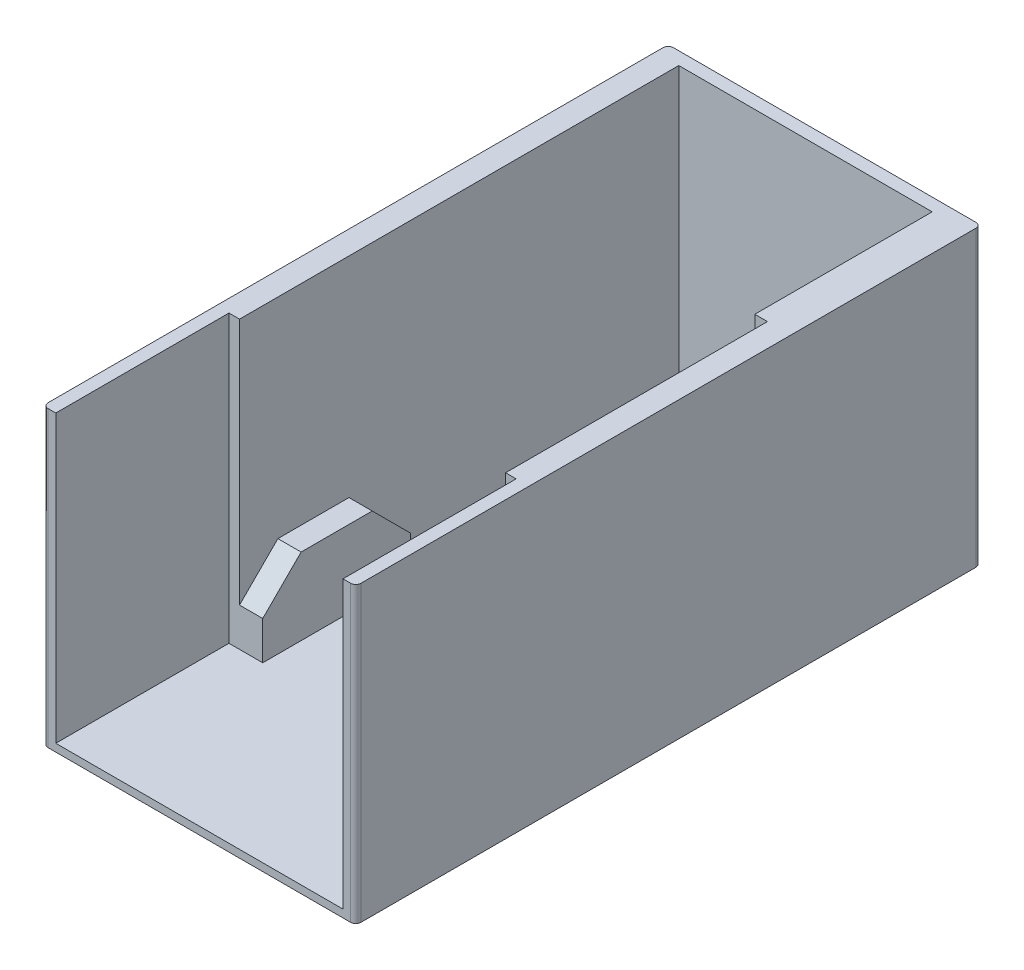
SolidWorks part; units mm, degrees
ref_plane "Front Plane" through (0, 0, 0) normal (0, 0, 1) x (1, 0, 0)
ref_plane "Top Plane" through (0, 0, 0) normal (0, 1, 0) x (1, 0, 0)
ref_plane "Right Plane" through (0, 0, 0) normal (1, 0, 0) x (0, 0, -1)
sketch "Sketch1" plane through (0, 0, 0) normal (0, 1, 0) x (1, 0, 0)
  line L0 (0, 0) -> (0, 2095.5) construction
  line L1 (-863.6, -520.7) -> (863.6, -520.7)
  line L2 (-863.6, -520.7) -> (-863.6, 520.7)
  line L3 (-863.6, 520.7) -> (863.6, 520.7)
  line L4 (863.6, -520.7) -> (863.6, 520.7)
  line L5 (-863.6, -520.7) -> (863.6, 520.7) construction
  line L6 (-863.6, 520.7) -> (863.6, -520.7) construction
  line L7 (-660.4, 520.7) -> (660.4, 520.7)
  line L8 (-660.4, 520.7) -> (-660.4, 1409.7)
  line L9 (-660.4, 1409.7) -> (660.4, 1409.7)
  line L10 (660.4, 520.7) -> (660.4, 1409.7)
  line L12 (-800.1, 1409.7) -> (800.1, 1409.7)
  line L13 (-800.1, 1409.7) -> (-800.1, 2095.5)
  line L14 (-800.1, 2095.5) -> (800.1, 2095.5)
  line L15 (800.1, 1409.7) -> (800.1, 2095.5)
  line L16 (-800.1, 2095.5) -> (723.9, 2095.5)
  line L17 (-800.1, 2095.5) -> (-800.1, 3162.3)
  line L18 (-800.1, 3162.3) -> (723.9, 3162.3)
  line L19 (723.9, 2095.5) -> (723.9, 3162.3)
  point P0 (0, 0)
  point P10 (0, 1409.7)
  point P13 (0, 2095.5)
  dimension "D1" = 1727.2
  dimension "D2" = 1041.4
  dimension "D3" = 1320.8
  dimension "D4" = 889
  dimension "D5" = 1600.2
  dimension "D6" = 685.8
  dimension "D7" = 1524
  dimension "D8" = 1066.8
sketch "Sketch2" plane through (0, 0, 0) normal (0, 1, 0) x (1, 0, 0)
  line L0 (-275, 3062.3) -> (-275, 3012.3) construction
  line L1 (-450, 3012.3) -> (-100, 3012.3)
  line L2 (-450, 3012.3) -> (-450, 2512.3)
  line L3 (-450, 2512.3) -> (-100, 2512.3)
  line L4 (-100, 3012.3) -> (-100, 2512.3)
  line L5 (-500, 3062.3) -> (-50, 3062.3)
  line L6 (-500, 3062.3) -> (-500, 2462.3)
  line L7 (-500, 2462.3) -> (-50, 2462.3)
  line L8 (-50, 3062.3) -> (-50, 2462.3)
  line L9 (-450, 2762.3) -> (-500, 2762.3) construction
  line L10 (100, 3012.3) -> (100, 2512.3)
  line L11 (100, 3012.3) -> (450, 3012.3)
  line L12 (450, 3012.3) -> (450, 2512.3)
  line L13 (100, 2512.3) -> (450, 2512.3)
  line L14 (50, 3062.3) -> (50, 2462.3)
  line L15 (50, 3062.3) -> (500, 3062.3)
  line L16 (500, 3062.3) -> (500, 2462.3)
  line L17 (50, 2462.3) -> (500, 2462.3)
  line L18 (100, 2312.3) -> (100, 1812.3)
  line L19 (100, 2312.3) -> (450, 2312.3)
  line L20 (450, 2312.3) -> (450, 1812.3)
  line L21 (100, 1812.3) -> (450, 1812.3)
  line L22 (50, 2362.3) -> (50, 1762.3)
  line L23 (50, 2362.3) -> (500, 2362.3)
  line L24 (500, 2362.3) -> (500, 1762.3)
  line L25 (50, 1762.3) -> (500, 1762.3)
  line L26 (100, 1612.3) -> (100, 1112.3)
  line L27 (100, 1612.3) -> (450, 1612.3)
  line L28 (450, 1612.3) -> (450, 1112.3)
  line L29 (100, 1112.3) -> (450, 1112.3)
  line L30 (50, 1662.3) -> (50, 1062.3)
  line L31 (50, 1662.3) -> (500, 1662.3)
  line L32 (500, 1662.3) -> (500, 1062.3)
  line L33 (50, 1062.3) -> (500, 1062.3)
  line L34 (100, 912.3) -> (100, 412.3)
  line L35 (100, 912.3) -> (450, 912.3)
  line L36 (450, 912.3) -> (450, 412.3)
  line L37 (100, 412.3) -> (450, 412.3)
  line L38 (50, 962.3) -> (50, 362.3)
  line L39 (50, 962.3) -> (500, 962.3)
  line L40 (500, 962.3) -> (500, 362.3)
  line L41 (50, 362.3) -> (500, 362.3)
  line L42 (-450, 2312.3) -> (-450, 1812.3)
  line L43 (-450, 2312.3) -> (-100, 2312.3)
  line L44 (-100, 2312.3) -> (-100, 1812.3)
  line L45 (-450, 1812.3) -> (-100, 1812.3)
  line L46 (-500, 2362.3) -> (-500, 1762.3)
  line L47 (-500, 2362.3) -> (-50, 2362.3)
  line L48 (-50, 2362.3) -> (-50, 1762.3)
  line L49 (-500, 1762.3) -> (-50, 1762.3)
  line L50 (-450, 1612.3) -> (-450, 1112.3)
  line L51 (-450, 1612.3) -> (-100, 1612.3)
  line L52 (-100, 1612.3) -> (-100, 1112.3)
  line L53 (-450, 1112.3) -> (-100, 1112.3)
  line L54 (-500, 1662.3) -> (-500, 1062.3)
  line L55 (-500, 1662.3) -> (-50, 1662.3)
  line L56 (-50, 1662.3) -> (-50, 1062.3)
  line L57 (-500, 1062.3) -> (-50, 1062.3)
  line L58 (-450, 912.3) -> (-450, 412.3)
  line L59 (-450, 912.3) -> (-100, 912.3)
  line L60 (-100, 912.3) -> (-100, 412.3)
  line L61 (-450, 412.3) -> (-100, 412.3)
  line L62 (-500, 962.3) -> (-500, 362.3)
  line L63 (-500, 962.3) -> (-50, 962.3)
  line L64 (-50, 962.3) -> (-50, 362.3)
  line L65 (-500, 362.3) -> (-50, 362.3)
  line L66 (-450, 3012.3) -> (100, 3012.3) construction
  line L67 (-450, 3012.3) -> (-450, 2312.3) construction
  line L68 (-50, 3062.3) -> (50, 3062.3) construction
  line L69 (0, 3062.3) -> (0, 2095.5) construction
  line L70 (-500, 2462.3) -> (-500, 2362.3)
  line L71 (-550, 3112.3) -> (550, 3112.3)
  line L72 (-550, 3112.3) -> (-550, 312.3)
  line L73 (-550, 312.3) -> (550, 312.3)
  line L74 (550, 3112.3) -> (550, 312.3)
  line L75 (-800.1, 3162.3) -> (723.9, 3162.3) construction
  dimension "D1" = 350
  dimension "D2" = 500
  dimension "D3" = 450
  dimension "D4" = 600
  dimension "D5" = 2
  dimension "D7" = 90
  dimension "D8" = 550
  dimension "D9" = 50
  dimension "D10" = 50
  dimension "D11" = 50
  dimension "D12" = 50
  dimension "D13" = 100
  dimension "D14" = 50
  dimension "D6" = 4
sketch "Resized Everything" plane through (0, 0, 0) normal (0, 1, 0) x (1, 0, 0)
  line L85 (-790.321, 2977.388) -> (-697.865, 2977.388)
  line L86 (-697.865, 2977.388) -> (-697.865, 3039.618)
  line L87 (-790.321, 3039.618) -> (-697.865, 3039.618)
  line L88 (-790.321, 2977.388) -> (-790.321, 3039.618)
  line L89 (-804.545, 2904.49) -> (-683.641, 2904.49)
  line L90 (-683.641, 2904.49) -> (-683.641, 2977.388)
  line L91 (-804.545, 2977.388) -> (-683.641, 2977.388)
  line L92 (-804.545, 2904.49) -> (-804.545, 2977.388)
  line L93 (-800.1, 3039.618) -> (-800.1, 3087.624)
  line L94 (-800.1, 3039.618) -> (-688.086, 3039.618)
  line L95 (-688.086, 3039.618) -> (-688.086, 3087.624)
  line L96 (-800.1, 3087.624) -> (-688.086, 3087.624)
  line L97 (-800.1, 3087.624) -> (-693.42, 3087.624)
  line L98 (-693.42, 3087.624) -> (-693.42, 3162.3)
  line L99 (-800.1, 3162.3) -> (-693.42, 3162.3)
  line L100 (-800.1, 3087.624) -> (-800.1, 3162.3)
  line L101 (-779.093, 3113.3) -> (-779.093, 3106.3)
  line L102 (-779.093, 3113.3) -> (-747.593, 3113.3)
  line L103 (-747.593, 3155.3) -> (-747.593, 3113.3)
  line L104 (-779.093, 3155.3) -> (-747.593, 3155.3)
  line L105 (-779.093, 3155.3) -> (-779.093, 3113.3)
  line L106 (-775.593, 3151.8) -> (-751.093, 3151.8)
  line L107 (-751.093, 3151.8) -> (-751.093, 3116.8)
  line L108 (-775.593, 3116.8) -> (-751.093, 3116.8)
  line L109 (-775.593, 3151.8) -> (-775.593, 3116.8)
  line L110 (-740.593, 3106.3) -> (-740.593, 3064.3)
  line L111 (-740.593, 3064.3) -> (-709.093, 3064.3)
  line L112 (-709.093, 3106.3) -> (-709.093, 3064.3)
  line L113 (-740.593, 3106.3) -> (-709.093, 3106.3)
  line L114 (-737.093, 3102.8) -> (-737.093, 3067.8)
  line L115 (-737.093, 3067.8) -> (-712.593, 3067.8)
  line L116 (-712.593, 3102.8) -> (-712.593, 3067.8)
  line L117 (-737.093, 3102.8) -> (-712.593, 3102.8)
  line L118 (-740.593, 3155.3) -> (-740.593, 3113.3)
  line L119 (-740.593, 3113.3) -> (-709.093, 3113.3)
  line L120 (-709.093, 3155.3) -> (-709.093, 3113.3)
  line L121 (-740.593, 3155.3) -> (-709.093, 3155.3)
  line L122 (-737.093, 3151.8) -> (-737.093, 3116.8)
  line L123 (-737.093, 3151.8) -> (-712.593, 3151.8)
  line L124 (-712.593, 3151.8) -> (-712.593, 3116.8)
  line L125 (-737.093, 3116.8) -> (-712.593, 3116.8)
  line L126 (-740.593, 3008.3) -> (-740.593, 2966.3)
  line L127 (-740.593, 2966.3) -> (-709.093, 2966.3)
  line L128 (-709.093, 3008.3) -> (-709.093, 2966.3)
  line L129 (-740.593, 3008.3) -> (-709.093, 3008.3)
  line L130 (-737.093, 3004.8) -> (-737.093, 2969.8)
  line L131 (-737.093, 2969.8) -> (-712.593, 2969.8)
  line L132 (-712.593, 3004.8) -> (-712.593, 2969.8)
  line L133 (-737.093, 3004.8) -> (-712.593, 3004.8)
  line L134 (-740.593, 3057.3) -> (-740.593, 3015.3)
  line L135 (-740.593, 3015.3) -> (-709.093, 3015.3)
  line L136 (-709.093, 3057.3) -> (-709.093, 3015.3)
  line L137 (-740.593, 3057.3) -> (-709.093, 3057.3)
  line L138 (-737.093, 3053.8) -> (-737.093, 3018.8)
  line L139 (-737.093, 3053.8) -> (-712.593, 3053.8)
  line L140 (-712.593, 3053.8) -> (-712.593, 3018.8)
  line L141 (-737.093, 3018.8) -> (-712.593, 3018.8)
  line L142 (-779.093, 3057.3) -> (-779.093, 3015.3)
  line L143 (-779.093, 3015.3) -> (-747.593, 3015.3)
  line L144 (-747.593, 3057.3) -> (-747.593, 3015.3)
  line L145 (-779.093, 3057.3) -> (-747.593, 3057.3)
  line L146 (-775.593, 3053.8) -> (-775.593, 3018.8)
  line L147 (-775.593, 3018.8) -> (-751.093, 3018.8)
  line L148 (-751.093, 3053.8) -> (-751.093, 3018.8)
  line L149 (-775.593, 3053.8) -> (-751.093, 3053.8)
  line L150 (-779.093, 3106.3) -> (-779.093, 3064.3)
  line L151 (-779.093, 3064.3) -> (-747.593, 3064.3)
  line L152 (-747.593, 3106.3) -> (-747.593, 3064.3)
  line L153 (-779.093, 3106.3) -> (-747.593, 3106.3)
  line L154 (-775.593, 3102.8) -> (-775.593, 3067.8)
  line L155 (-775.593, 3102.8) -> (-751.093, 3102.8)
  line L156 (-751.093, 3102.8) -> (-751.093, 3067.8)
  line L157 (-775.593, 3067.8) -> (-751.093, 3067.8)
  line L158 (-782.593, 3158.8) -> (-705.593, 3158.8)
  line L159 (-705.593, 3158.8) -> (-705.593, 2962.8)
  line L160 (-782.593, 2962.8) -> (-705.593, 2962.8)
  line L161 (-782.593, 3158.8) -> (-782.593, 2962.8)
  line L162 (-779.093, 3008.3) -> (-779.093, 2966.3)
  line L163 (-779.093, 2966.3) -> (-747.593, 2966.3)
  line L164 (-747.593, 3008.3) -> (-747.593, 2966.3)
  line L165 (-779.093, 3008.3) -> (-747.593, 3008.3)
  line L166 (-775.593, 3004.8) -> (-775.593, 2969.8)
  line L167 (-775.593, 3004.8) -> (-751.093, 3004.8)
  line L168 (-751.093, 3004.8) -> (-751.093, 2969.8)
  line L169 (-775.593, 2969.8) -> (-751.093, 2969.8)
sketch "Sketch6" plane through (0, 0, 0) normal (0, 1, 0) x (1, 0, 0)
  line L0 (-800.1, 3162.3) -> (723.9, 3162.3) construction
  line L1 (-748.0935, 2917.905) -> (-748.0935, 3167.3) construction
  line L2 (-809.2275, 2917.905) -> (-686.9595, 2917.905)
  line L3 (-686.9595, 2917.905) -> (-686.9595, 3167.3)
  line L4 (-686.9595, 3167.3) -> (-809.2275, 3167.3)
  line L5 (-696.087, 3048.381) -> (-696.087, 2990.596)
  line L6 (-800.1, 3048.381) -> (-800.1, 2990.596)
  line L7 (-809.2275, 2917.905) -> (-809.2275, 3167.3)
  line L8 (-701.04, 3162.3) -> (-696.087, 3162.3)
  line L9 (-696.087, 3162.3) -> (-696.087, 3092.958)
  line L10 (-804.2275, 2922.905) -> (-809.2275, 2922.905)
  line L11 (-691.9595, 2922.905) -> (-686.9595, 2922.905)
  line L16 (-791.0195, 2990.596) -> (-705.1675, 2990.596)
  line L17 (-705.1675, 2990.596) -> (-705.1675, 3048.381)
  line L18 (-791.0195, 3048.381) -> (-705.1675, 3048.381)
  line L19 (-791.0195, 2990.596) -> (-791.0195, 3048.381)
  line L20 (-804.2275, 2922.905) -> (-691.9595, 2922.905)
  line L21 (-691.9595, 2922.905) -> (-691.9595, 2990.596)
  line L22 (-804.2275, 2990.596) -> (-691.9595, 2990.596)
  line L23 (-804.2275, 2922.905) -> (-804.2275, 2990.596)
  line L24 (-800.1, 3048.381) -> (-800.1, 3092.958)
  line L25 (-800.1, 3048.381) -> (-696.087, 3048.381)
  line L26 (-696.087, 3048.381) -> (-696.087, 3092.958)
  line L27 (-800.1, 3092.958) -> (-696.087, 3092.958)
  line L28 (-800.1, 3092.958) -> (-701.04, 3092.958)
  line L29 (-701.04, 3092.958) -> (-701.04, 3162.3)
  line L30 (-800.1, 3162.3) -> (-701.04, 3162.3)
  line L31 (-800.1, 3092.958) -> (-800.1, 3162.3)
  point P3 (-748.0935, 2922.905)
  dimension "D1" = 239.395
  dimension "D2" = 5
  dimension "D3" = 5
  dimension "D4" = 5
extrude "Boss-Extrude1" add sketch "Sketch6" along normal blind 111.8 contours L2 L1 L20 L23 L22 L6 L24 L31 L30 L4 L7 | L1 L2 L3 L4 L30 L29 L27 L26 L5 L22 L21 L20 | L29 L27 L9 L8 region at (-801.3852, 0, -3070.3406) region at (-694.8018, 0, -3070.3406) region at (-698.5635, 0, -3127.629)
sketch "Sketch7" plane through (0, 0, 0) normal (0, -1, 0) x (1, 0, 0)
  line L0 (-800.1, -3048.381) -> (-800.1, -2990.596) construction
  line L1 (-696.087, -3048.381) -> (-696.087, -2990.596) construction
  line L2 (-800.1, -3048.381) -> (-800.1, -3092.958) construction
  line L3 (-800.1, -3092.958) -> (-696.087, -3092.958) construction
  line L4 (-800.1, -3092.958) -> (-701.04, -3092.958) construction
  line L5 (-701.04, -3092.958) -> (-701.04, -3162.3) construction
  line L6 (-800.1, -3162.3) -> (-701.04, -3162.3) construction
  line L7 (-800.1, -3092.958) -> (-800.1, -3162.3) construction
  line L8 (-701.04, -3162.3) -> (-696.087, -3162.3) construction
  line L9 (-696.087, -3162.3) -> (-696.087, -3092.958) construction
  line L10 (-696.087, -3048.381) -> (-696.087, -3092.958) construction
  line L11 (-800.1, -3048.381) -> (-696.087, -3048.381) construction
  line L12 (-809.2275, -2917.905) -> (-686.9595, -2917.905) construction
  line L13 (-686.9595, -2917.905) -> (-686.9595, -3167.3) construction
  line L14 (-686.9595, -3167.3) -> (-809.2275, -3167.3) construction
  line L15 (-809.2275, -2917.905) -> (-809.2275, -3167.3) construction
  line L16 (-804.2275, -2922.905) -> (-691.9595, -2922.905) construction
  line L17 (-691.9595, -2922.905) -> (-691.9595, -2990.596) construction
  line L18 (-804.2275, -2990.596) -> (-691.9595, -2990.596) construction
  line L19 (-804.2275, -2922.905) -> (-804.2275, -2990.596) construction
  line L20 (-705.1675, -2990.596) -> (-705.1675, -3048.381) construction
  line L21 (-791.0195, -3048.381) -> (-705.1675, -3048.381) construction
  line L22 (-791.0195, -2990.596) -> (-791.0195, -3048.381) construction
  line L23 (-791.0195, -2990.596) -> (-705.1675, -2990.596) construction
  line L24 (-800.1, -3048.381) -> (-800.1, -2990.596)
  line L25 (-696.087, -3048.381) -> (-696.087, -2990.596)
  line L26 (-800.1, -3048.381) -> (-800.1, -3092.958)
  line L27 (-800.1, -3092.958) -> (-696.087, -3092.958)
  line L28 (-800.1, -3092.958) -> (-701.04, -3092.958)
  line L29 (-701.04, -3092.958) -> (-701.04, -3162.3)
  line L30 (-800.1, -3162.3) -> (-701.04, -3162.3)
  line L31 (-800.1, -3092.958) -> (-800.1, -3162.3)
  line L32 (-701.04, -3162.3) -> (-696.087, -3162.3)
  line L33 (-696.087, -3162.3) -> (-696.087, -3092.958)
  line L34 (-696.087, -3048.381) -> (-696.087, -3092.958)
  line L35 (-800.1, -3048.381) -> (-696.087, -3048.381)
  line L36 (-809.2275, -2917.905) -> (-686.9595, -2917.905)
  line L37 (-686.9595, -2917.905) -> (-686.9595, -3167.3)
  line L38 (-686.9595, -3167.3) -> (-809.2275, -3167.3)
  line L39 (-809.2275, -2917.905) -> (-809.2275, -3167.3)
  line L40 (-804.2275, -2922.905) -> (-691.9595, -2922.905)
  line L41 (-691.9595, -2922.905) -> (-691.9595, -2990.596)
  line L42 (-804.2275, -2990.596) -> (-691.9595, -2990.596)
  line L43 (-804.2275, -2922.905) -> (-804.2275, -2990.596)
  line L44 (-705.1675, -2990.596) -> (-705.1675, -3048.381)
  line L45 (-791.0195, -3048.381) -> (-705.1675, -3048.381)
  line L46 (-791.0195, -2990.596) -> (-791.0195, -3048.381)
  line L47 (-791.0195, -2990.596) -> (-705.1675, -2990.596)
extrude "Boss-Extrude2" add sketch "Sketch7" along normal blind 3 contours L39 L38 L37 L36
sketch "Sketch8" plane through (0, 0, 0) normal (0, 1, 0) x (1, 0, 0)
  line L0 (-691.9595, 2922.905) -> (-686.9595, 2922.905) construction
  line L1 (-804.2275, 2922.905) -> (-809.2275, 2922.905) construction
  line L2 (-800.1, 3048.381) -> (-800.1, 2990.596) construction
  line L3 (-696.087, 3048.381) -> (-696.087, 2990.596) construction
  line L4 (-800.1, 3048.381) -> (-800.1, 3092.958) construction
  line L5 (-800.1, 3092.958) -> (-696.087, 3092.958) construction
  line L6 (-800.1, 3092.958) -> (-701.04, 3092.958) construction
  line L7 (-701.04, 3092.958) -> (-701.04, 3162.3) construction
  line L8 (-800.1, 3162.3) -> (-701.04, 3162.3) construction
  line L9 (-800.1, 3092.958) -> (-800.1, 3162.3) construction
  line L10 (-804.2275, 2922.905) -> (-691.9595, 2922.905) construction
  line L11 (-691.9595, 2922.905) -> (-691.9595, 2990.596) construction
  line L12 (-804.2275, 2990.596) -> (-691.9595, 2990.596) construction
  line L13 (-804.2275, 2922.905) -> (-804.2275, 2990.596) construction
  line L14 (-701.04, 3162.3) -> (-696.087, 3162.3) construction
  line L15 (-696.087, 3162.3) -> (-696.087, 3092.958) construction
  line L16 (-696.087, 3048.381) -> (-696.087, 3092.958) construction
  line L17 (-800.1, 3048.381) -> (-696.087, 3048.381) construction
  line L18 (-809.2275, 2917.905) -> (-686.9595, 2917.905) construction
  line L19 (-686.9595, 2917.905) -> (-686.9595, 3167.3) construction
  line L20 (-686.9595, 3167.3) -> (-809.2275, 3167.3) construction
  line L21 (-809.2275, 2917.905) -> (-809.2275, 3167.3) construction
  line L22 (-705.1675, 2990.596) -> (-705.1675, 3048.381) construction
  line L23 (-791.0195, 3048.381) -> (-705.1675, 3048.381) construction
  line L24 (-791.0195, 2990.596) -> (-791.0195, 3048.381) construction
  line L25 (-791.0195, 2990.596) -> (-705.1675, 2990.596) construction
  line L26 (-691.9595, 2922.905) -> (-686.9595, 2922.905)
  line L27 (-804.2275, 2922.905) -> (-809.2275, 2922.905)
  line L28 (-800.1, 3048.381) -> (-800.1, 2990.596)
  line L29 (-696.087, 3048.381) -> (-696.087, 2990.596)
  line L30 (-800.1, 3048.381) -> (-800.1, 3092.958)
  line L31 (-800.1, 3092.958) -> (-696.087, 3092.958)
  line L32 (-800.1, 3092.958) -> (-701.04, 3092.958)
  line L33 (-701.04, 3092.958) -> (-701.04, 3162.3)
  line L34 (-800.1, 3162.3) -> (-701.04, 3162.3)
  line L35 (-800.1, 3092.958) -> (-800.1, 3162.3)
  line L36 (-804.2275, 2922.905) -> (-691.9595, 2922.905)
  line L37 (-691.9595, 2922.905) -> (-691.9595, 2990.596)
  line L38 (-804.2275, 2990.596) -> (-691.9595, 2990.596)
  line L39 (-804.2275, 2922.905) -> (-804.2275, 2990.596)
  line L40 (-701.04, 3162.3) -> (-696.087, 3162.3)
  line L41 (-696.087, 3162.3) -> (-696.087, 3092.958)
  line L42 (-696.087, 3048.381) -> (-696.087, 3092.958)
  line L43 (-800.1, 3048.381) -> (-696.087, 3048.381)
  line L44 (-809.2275, 2917.905) -> (-686.9595, 2917.905)
  line L45 (-686.9595, 2917.905) -> (-686.9595, 3167.3)
  line L46 (-686.9595, 3167.3) -> (-809.2275, 3167.3)
  line L47 (-809.2275, 2917.905) -> (-809.2275, 3167.3)
  line L48 (-705.1675, 2990.596) -> (-705.1675, 3048.381)
  line L49 (-791.0195, 3048.381) -> (-705.1675, 3048.381)
  line L50 (-791.0195, 2990.596) -> (-791.0195, 3048.381)
  line L51 (-791.0195, 2990.596) -> (-705.1675, 2990.596)
  line M17 (-696.087, 2990.596) -> (-696.087, 3092.958)
  line M21 (-800.1, 3162.3) -> (-800.1, 2990.596)
extrude "Boss-Extrude3" add sketch "Sketch8" along normal blind 30 contours L38 L50 L43 M21 | L48 L38 L43 M17 region at (-700.6273, 0, -3019.4885) region at (-795.5597, 0, -3019.4885)
ref_plane "Plane1" through (-748.0935, 0, 0) normal (1, 0, 0) x (0, 0, -1)
sketch "Sketch9" plane through (-791.0195, 0, 0) normal (1, 0, 0) x (0, 0, -1)
  line L0 (2990.596, 15) -> (3005.596, 30)
  line L1 (3019.4885, 30) -> (3019.4885, 0) construction
  line L2 (3048.381, 15) -> (3033.381, 30)
  line L4 (2990.596, 0) -> (3048.381, 0)
  line L5 (3048.381, 0) -> (3048.381, 30)
  line L6 (3048.381, 30) -> (2990.596, 30)
  line L7 (2990.596, 30) -> (2990.596, 0)
  line L8 (2990.596, 0) -> (3048.381, 0)
  line L9 (3048.381, 0) -> (3048.381, 30)
  line L10 (3048.381, 30) -> (2990.596, 30)
  line L11 (2990.596, 30) -> (2990.596, 0)
  line M8 (3048.381, 0) -> (3048.381, 30)
  line M9 (3048.381, 30) -> (2990.596, 30)
  line M10 (2990.596, 30) -> (2990.596, 0)
  dimension "D2" = 45
  dimension "D1" = 0
extrude "Cut-Extrude1" cut sketch "Sketch9" against normal up to surface (9.0805 mm away) contours L0 M10 M9 | L2 M8 M9 region at (-791.0195, 25, -2995.596) region at (-791.0195, 25, -3043.381) up to face at (-800.1, 47.2667, -3067.0923)
sketch "Sketch10" plane through (-705.1675, 0, 0) normal (-1, 0, 0) x (0, 0, 1)
  line L0 (-3048.381, 15) -> (-3033.381, 30) construction
  line L1 (-2990.596, 15) -> (-3005.596, 30) construction
  line L2 (-3048.381, 15) -> (-3033.381, 30)
  line L3 (-2990.596, 15) -> (-3005.596, 30)
  line L4 (-3048.381, 0) -> (-2990.596, 0)
  line L5 (-3048.381, 30) -> (-3048.381, 0)
  line L6 (-2990.596, 30) -> (-3048.381, 30)
  line L7 (-2990.596, 0) -> (-2990.596, 30)
  line L8 (-3048.381, 0) -> (-2990.596, 0)
  line L9 (-3048.381, 30) -> (-3048.381, 0)
  line L10 (-2990.596, 30) -> (-3048.381, 30)
  line L11 (-2990.596, 0) -> (-2990.596, 30)
  line M6 (-2990.596, 0) -> (-2990.596, 30)
  line M7 (-2990.596, 30) -> (-3048.381, 30)
  line M8 (-3048.381, 30) -> (-3048.381, 0)
  dimension "D1" = 0
extrude "Cut-Extrude2" cut sketch "Sketch10" against normal up to surface (9.0805 mm away) contours L2 M8 M7 | L3 M6 M7 region at (-705.1675, 25, -3043.381) region at (-705.1675, 25, -2995.596) up to face at (-696.087, 47.2667, -3043.9783)
fillet "Fillet1" radius 2 4 edges at (-686.9595, 55.9, -2922.905) (-686.9595, 54.4, -3167.3) (-809.2275, 54.4, -3167.3) (-809.2275, 55.9, -2922.905) tangent propagation no
sketch "Sketch11" plane through (0, 0, 0) normal (0, 1, 0) x (-1, 0, 0)
  line L0 (804.2275, -2922.905) -> (691.9595, -2922.905)
  line L18 (791.0195, -3048.381) -> (791.0195, -2990.596)
  line L19 (791.0195, -2990.596) -> (804.2275, -2990.596)
  line L20 (804.2275, -2990.596) -> (804.2275, -2922.905)
  line L21 (804.2275, -2922.905) -> (807.2275, -2922.905)
  line L22 (809.2275, -2924.905) -> (809.2275, -2917.905)
  line L23 (809.2275, -2917.905) -> (686.9595, -2917.905)
  line L24 (686.9595, -2917.905) -> (686.9595, -2924.905)
  line L25 (688.9595, -2922.905) -> (691.9595, -2922.905)
  line L26 (691.9595, -2922.905) -> (691.9595, -2990.596)
  line L27 (691.9595, -2990.596) -> (705.1675, -2990.596)
  line L28 (705.1675, -2990.596) -> (705.1675, -3048.381)
  line L29 (705.1675, -3048.381) -> (696.087, -3048.381)
  line L30 (696.087, -3048.381) -> (696.087, -3092.958)
  line L31 (696.087, -3092.958) -> (701.04, -3092.958)
  line L32 (701.04, -3092.958) -> (701.04, -3162.3)
  line L33 (701.04, -3162.3) -> (800.1, -3162.3)
  line L34 (800.1, -3162.3) -> (800.1, -3048.381)
  line L35 (800.1, -3048.381) -> (791.0195, -3048.381)
  line L36 (791.0195, -3048.381) -> (791.0195, -2990.596)
  line L37 (791.0195, -2990.596) -> (804.2275, -2990.596)
  line L38 (804.2275, -2990.596) -> (804.2275, -2922.905)
  line L39 (804.2275, -2922.905) -> (807.2275, -2922.905)
  line L40 (809.2275, -2924.905) -> (809.2275, -2917.905)
  line L41 (809.2275, -2917.905) -> (686.9595, -2917.905)
  line L42 (686.9595, -2917.905) -> (686.9595, -2924.905)
  line L43 (688.9595, -2922.905) -> (691.9595, -2922.905)
  line L44 (691.9595, -2922.905) -> (691.9595, -2990.596)
  line L45 (691.9595, -2990.596) -> (705.1675, -2990.596)
  line L46 (705.1675, -2990.596) -> (705.1675, -3048.381)
  line L47 (705.1675, -3048.381) -> (696.087, -3048.381)
  line L48 (696.087, -3048.381) -> (696.087, -3092.958)
  line L49 (696.087, -3092.958) -> (701.04, -3092.958)
  line L50 (701.04, -3092.958) -> (701.04, -3162.3)
  line L51 (701.04, -3162.3) -> (800.1, -3162.3)
  line L52 (800.1, -3162.3) -> (800.1, -3048.381)
  line L53 (800.1, -3048.381) -> (791.0195, -3048.381)
  arc A2 (809.2275, -2924.905) -> (807.2275, -2922.905) centre (807.2275, -2924.905) ccw
  arc A3 (688.9595, -2922.905) -> (686.9595, -2924.905) centre (688.9595, -2924.905) ccw
  arc A4 (809.2275, -2924.905) -> (807.2275, -2922.905) centre (807.2275, -2924.905) ccw
  arc A5 (688.9595, -2922.905) -> (686.9595, -2924.905) centre (688.9595, -2924.905) ccw
  line M24 (804.2275, -2922.905) -> (807.2275, -2922.905)
  arc M25 (807.2275, -2922.905) -> (809.2275, -2924.905) centre (807.2275, -2924.905) cw
  line M26 (809.2275, -2924.905) -> (809.2275, -2917.905)
  line M27 (809.2275, -2917.905) -> (686.9595, -2917.905)
  line M28 (686.9595, -2917.905) -> (686.9595, -2924.905)
  arc M29 (686.9595, -2924.905) -> (688.9595, -2922.905) centre (688.9595, -2924.905) cw
  line M30 (688.9595, -2922.905) -> (691.9595, -2922.905)
  dimension "D1" = 0
extrude "Cut-Extrude3" cut sketch "Sketch11" against normal through all contours L0 M24 M25 M26 M27 M28 M29 M30 region at (-748.0935, 0, -2920.4133)
equation "\"alpha\"= 1"
equation "\"bin_width\"= 0.5"
equation "\"bin_depth\"= 0.35"
equation "\"bin_height\"= 0.35"
